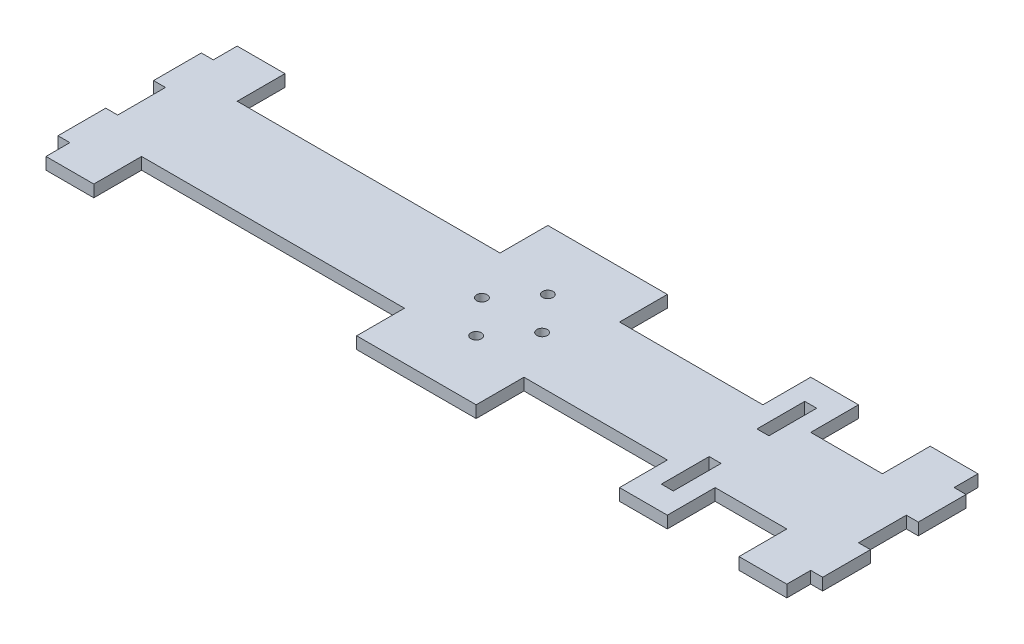
SolidWorks part; units mm, degrees
ref_plane "Front Plane" through (0, 0, 0) normal (0, 0, 1) x (1, 0, 0)
ref_plane "Top Plane" through (0, 0, 0) normal (0, 1, 0) x (1, 0, 0)
ref_plane "Right Plane" through (0, 0, 0) normal (1, 0, 0) x (0, 0, -1)
sketch "Sketch1" plane through (0, 0, 0) normal (0, 1, 0) x (1, 0, 0)
  line L6 (82.55, 31.75) -> (82.55, 44.45)
  line L7 (82.55, 44.45) -> (114.3, 44.45)
  line L8 (114.3, 44.45) -> (114.3, 31.75)
  line L20 (114.3, 6.35) -> (114.3, -6.35)
  line L21 (114.3, -6.35) -> (82.55, -6.35)
  line L22 (82.55, -6.35) -> (82.55, 6.35)
  line L28 (0, 44.45) -> (0, 38.1)
  line L29 (98.425, 19.05) -> (106.426, 19.05) construction
  line L30 (98.425, 19.05) -> (90.424, 19.05) construction
  line L31 (98.425, 28.575) -> (98.425, 19.05) construction
  line L32 (158.75, 38.1) -> (158.75, 44.45) construction
  line L33 (98.425, 19.05) -> (98.425, 9.525) construction
  line L34 (12.7, 31.75) -> (82.55, 31.75)
  line L35 (12.7, 6.35) -> (82.55, 6.35)
  line L36 (12.7, 6.35) -> (12.7, -6.35)
  line L37 (12.7, -6.35) -> (0, -6.35)
  line L38 (0, -6.35) -> (0, 0)
  line L39 (0, 0) -> (-3.175, 0)
  line L40 (-3.175, 0) -> (-3.175, 12.7)
  line L41 (-3.175, 12.7) -> (0, 12.7)
  line L42 (0, 12.7) -> (0, 25.4)
  line L43 (0, 25.4) -> (-3.175, 25.4)
  line L44 (-3.175, 25.4) -> (-3.175, 38.1)
  line L45 (-3.175, 38.1) -> (0, 38.1)
  line L47 (0, 44.45) -> (12.7, 44.45)
  line L48 (12.7, 44.45) -> (12.7, 31.75)
  line L50 (152.4, 6.35) -> (152.4, -6.35)
  line L51 (152.4, -6.35) -> (165.1, -6.35)
  line L52 (165.1, -6.35) -> (165.1, 6.35)
  line L53 (165.1, 6.35) -> (184.15, 6.35)
  line L54 (184.15, 6.35) -> (184.15, -6.35)
  line L55 (184.15, -6.35) -> (196.85, -6.35)
  line L56 (196.85, -6.35) -> (196.85, 0)
  line L57 (196.85, 0) -> (200.025, 0)
  line L58 (200.025, 0) -> (200.025, 12.7)
  line L59 (200.025, 12.7) -> (196.85, 12.7)
  line L60 (196.85, 12.7) -> (196.85, 25.4)
  line L61 (196.85, 25.4) -> (200.025, 25.4)
  line L62 (200.025, 25.4) -> (200.025, 38.1)
  line L63 (200.025, 38.1) -> (196.85, 38.1)
  line L64 (196.85, 38.1) -> (196.85, 44.45)
  line L65 (196.85, 44.45) -> (184.15, 44.45)
  line L66 (184.15, 44.45) -> (184.15, 31.75)
  line L67 (184.15, 31.75) -> (165.1, 31.75)
  line L68 (165.1, 31.75) -> (165.1, 44.45)
  line L69 (165.1, 44.45) -> (152.4, 44.45)
  line L70 (152.4, 44.45) -> (152.4, 31.75)
  line L71 (152.4, 31.75) -> (114.3, 31.75)
  line L72 (158.75, 12.7) -> (158.75, 25.4) construction
  line L73 (157.1625, 0) -> (160.3375, 0)
  line L74 (157.1625, 0) -> (157.1625, 12.7)
  line L75 (157.1625, 12.7) -> (160.3375, 12.7)
  line L76 (160.3375, 0) -> (160.3375, 12.7)
  line L77 (157.1625, 25.4) -> (160.3375, 25.4)
  line L78 (157.1625, 25.4) -> (157.1625, 38.1)
  line L79 (157.1625, 38.1) -> (160.3375, 38.1)
  line L80 (160.3375, 25.4) -> (160.3375, 38.1)
  line L81 (158.75, 19.05) -> (196.85, 19.05) construction
  line L82 (114.3, 6.35) -> (152.4, 6.35)
  circle A0 centre (90.424, 19.05) radius 1.397
  circle A1 centre (106.426, 19.05) radius 1.397
  circle A2 centre (98.425, 28.575) radius 1.397
  circle A3 centre (98.425, 9.525) radius 1.397
  dimension "D9" = 12.7
  dimension "D26" = 2.794
  dimension "D1" = 3.175
  dimension "D2" = 12.7
  dimension "D3" = 12.7
  dimension "D4" = 196.85
  dimension "D5" = 12.7
  dimension "D6" = 12.7
  dimension "D7" = 3.175
  dimension "D8" = 12.7
  dimension "D10" = 25.4
  dimension "D11" = 69.85
  dimension "D12" = 3.175
  dimension "D13" = 12.7
  dimension "D14" = 12.7
  dimension "D15" = 12.7
  dimension "D16" = 12.7
  dimension "D17" = 19.05
  dimension "D18" = 69.85
  dimension "D19" = 12.7
  dimension "D20" = 50.8
  dimension "D21" = 25.4
  dimension "D22" = 15.875
  dimension "D23" = 16.002
  dimension "D24" = 6.35
  dimension "D25" = 19.05
  dimension "D27" = 25.4
  dimension "D28" = 69.85
extrude "Boss-Extrude1" add sketch "Sketch1" along normal blind 3.175
